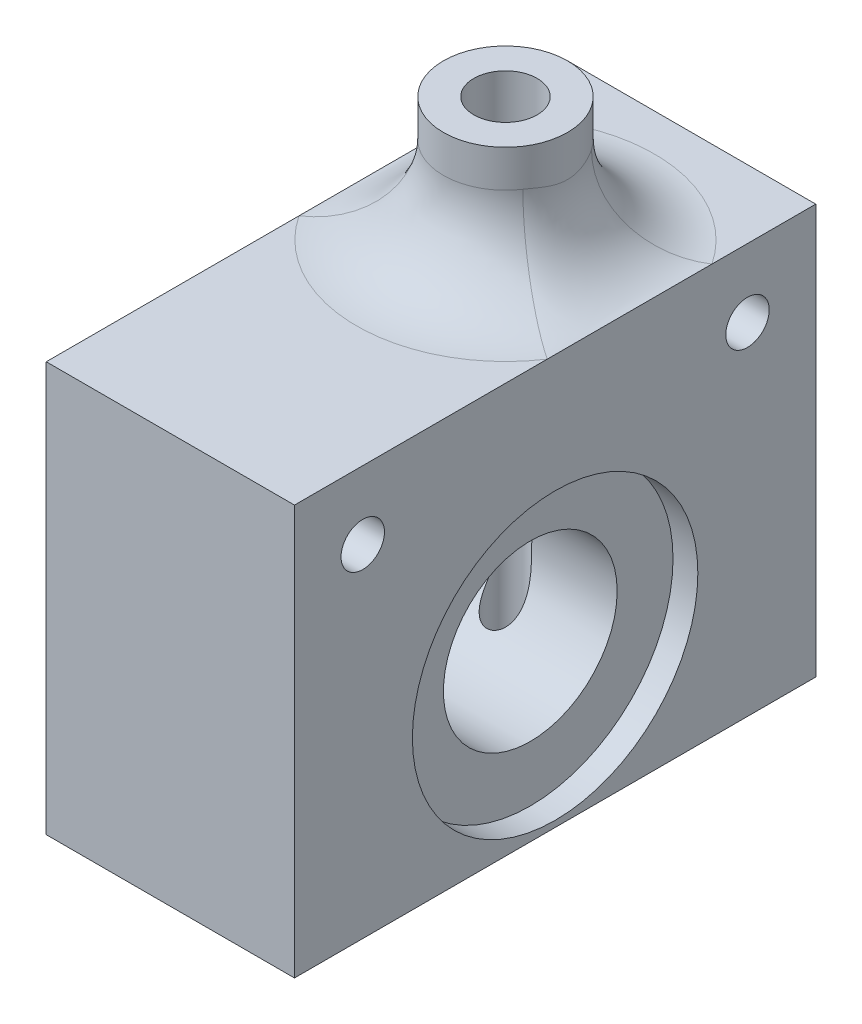
SolidWorks part; units mm, degrees
ref_plane "Front Plane" through (0, 0, 0) normal (0, 0, 1) x (1, 0, 0)
ref_plane "Top Plane" through (0, 0, 0) normal (0, 1, 0) x (1, 0, 0)
ref_plane "Right Plane" through (0, 0, 0) normal (1, 0, 0) x (0, 0, -1)
sketch "Sketch1" plane through (0, 0, 0) normal (1, 0, 0) x (0, 0, -1)
  line L1 (-21, -12) -> (21, -12)
  line L2 (-21, -12) -> (-21, 21)
  line L3 (-21, 21) -> (21, 21)
  line L4 (21, -12) -> (21, 21)
  line L5 (15.5, 15.5) -> (21, 15.5) construction
  line L6 (15.5, 15.5) -> (15.5, 21) construction
  line L7 (15.5, 21) -> (21, 21)
  line L8 (21, 15.5) -> (21, 21)
  line L9 (-15.5, 15.5) -> (-21, 15.5) construction
  line L10 (-15.5, 15.5) -> (-15.5, 21) construction
  line L11 (-15.5, 21) -> (-21, 21)
  line L12 (-21, 15.5) -> (-21, 21)
  circle A0 centre (0, 0) radius 7
  circle A2 centre (15.5, 15.5) radius 1.75
  circle A4 centre (-15.5, 15.5) radius 1.75
  point P10 (0, -12)
  dimension "D4" = 14
  dimension "D7" = 3.5
  dimension "D1" = 42
  dimension "D2" = 33
  dimension "D3" = 12
  dimension "D5" = 5.5
extrude "Boss-Extrude1" add sketch "Sketch1" along normal mid plane 20 contours L1 L4 L3 L2 A4 A2 A0 region at (0, 1.75, 20.4659)
sketch "Sketch2" plane through (10, 0, 0) normal (1, 0, 0) x (0, 0, -1)
  circle A0 centre (0, 0) radius 11.5
  dimension "D1" = 23
extrude "Cut-Extrude1" cut sketch "Sketch2" against normal blind 2
sketch "Sketch3" plane through (0, 21, 0) normal (0, 1, 0) x (1, 0, 0)
  line L1 (10, -21) -> (-10, -21) construction
  line L2 (0, -23.1) -> (0, 23.1) construction
  circle A0 centre (0, 6) radius 1.5
  circle A1 centre (0, 6) radius 5
  circle A2 centre (0, 6) radius 2.55
  point P6 (-5.822, 5)
  dimension "D1" = 3
  dimension "D2" = 10
  dimension "D3" = 5.1
  dimension "D4" = 27
extrude "Cut-Extrude2" cut sketch "Sketch3" against normal through all both and the other way through all contours A0 region at (0, 21, -6)
extrude "Boss-Extrude2" add sketch "Sketch3<3>" along normal blind 10 contours A1 A2 region at (-4.8586, 21, -6)
sketch "Sketch3<3>" plane through (0, 21, 0) normal (0, 1, 0) x (1, 0, 0) same geometry as "Sketch3"
fillet "Fillet1" radius 7 1 edges at (0, 21, -1)
